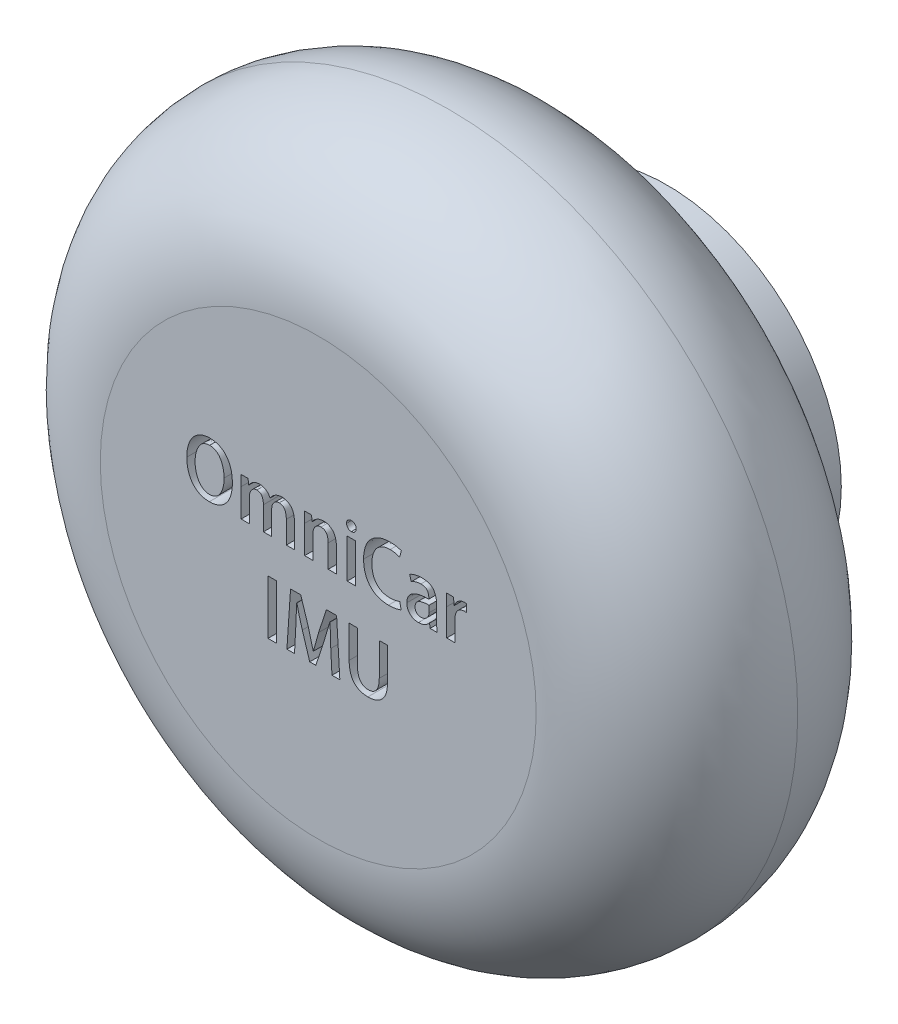
SolidWorks part; units mm, degrees
ref_plane "前视基准面" through (0, 0, 0) normal (0, 0, 1) x (1, 0, 0)
ref_plane "上视基准面" through (0, 0, 0) normal (0, 1, 0) x (1, 0, 0)
ref_plane "右视基准面" through (0, 0, 0) normal (1, 0, 0) x (0, 0, -1)
other "Configuration Table"
sketch "草图1" plane through (0, 0, 0) normal (0, 0, 1) x (1, 0, 0)
  circle A0 centre (0, 0) radius 400
  dimension "D1" = 800
extrude "凸台-拉伸1" add sketch "草图1" along normal blind 300
fillet "圆角1" radius 150 2 edges at (400, 0, 300) (400, 0, 0)
sketch "草图2" plane through (0, 0, 300) normal (0, 0, 1) x (1, 0, 0)
  text T0 "<b>OmniCar</b>\r\n<b>     IMU</b>" font "@Adobe 繁黑體 Std B" height in points 200
extrude "切除-拉伸1" cut sketch "草图2" against normal blind 100
sketch "草图3" plane through (0, 0, 0) normal (0, 0, -1) x (-1, 0, 0)
  circle A0 centre (0, 0) radius 200
  dimension "D1" = 400
extrude "凸台-拉伸2" add sketch "草图3" along normal blind 100
